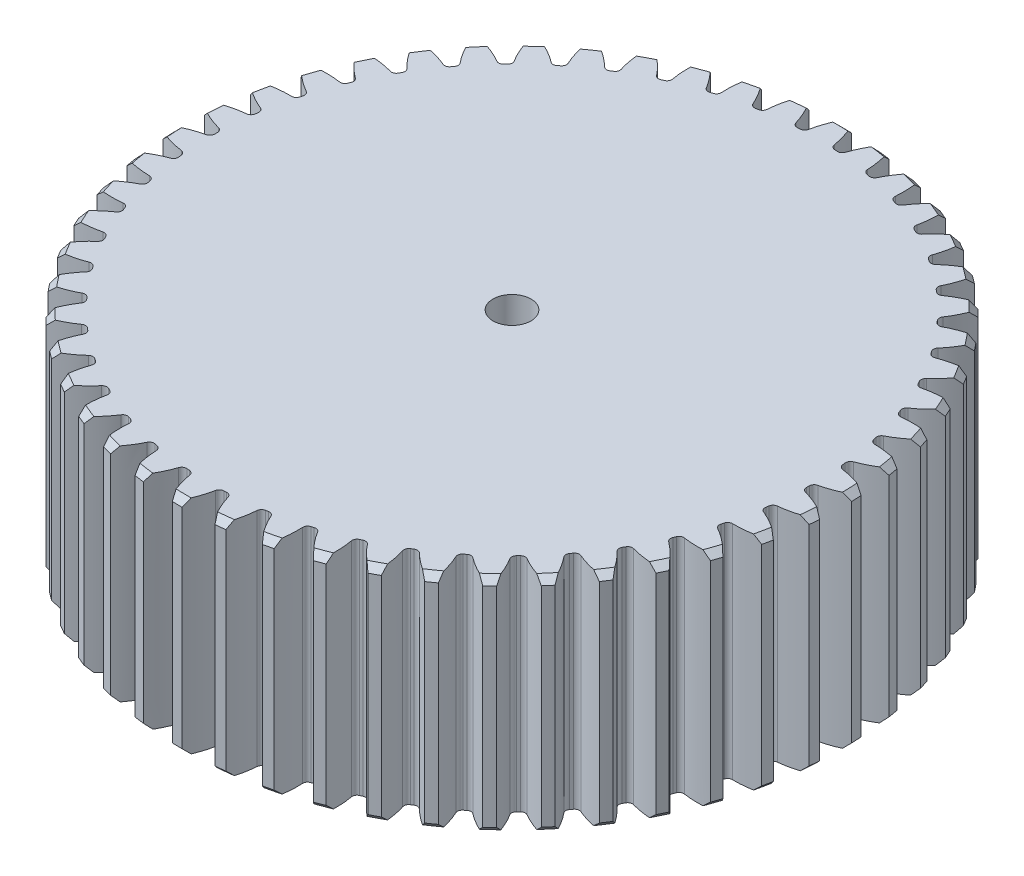
SolidWorks part; units mm, degrees
ref_plane "前视基准面" through (0, 0, 0) normal (0, 0, 1) x (1, 0, 0)
ref_plane "上视基准面" through (0, 0, 0) normal (0, 1, 0) x (1, 0, 0)
ref_plane "右视基准面" through (0, 0, 0) normal (1, 0, 0) x (0, 0, -1)
other "Configuration Table"
sketch "草图2" plane through (0, 0, 0) normal (0, 1, 0) x (1, 0, 0)
  spline S0 degree 4 poles (46.9846, 0) (47.0061, 0.0004) (47.0661, 0.0025) (47.1796, 0.0108) (47.3643, 0.0305) (47.5989, 0.0648) (47.901, 0.1194) (48.2551, 0.197) (48.6421, 0.2962) (49.0604, 0.4189) (49.475, 0.5545) (49.8857, 0.7017) (50.2924, 0.8595) (50.7812, 1.0629) (51.3631, 1.3253) (52.034, 1.6561) (52.7871, 2.0634) (53.5397, 2.5066) (54.2754, 2.9735) (54.9982, 3.466) (55.7019, 3.9762) (56.3971, 4.5131) (56.9817, 4.989) (57.4902, 5.4247) (57.8815, 5.7686) (58.2355, 6.0926) (58.5753, 6.4044) (59.1303, 6.942) (59.4711, 7.2816) (59.9928, 7.8193) (60.1778, 8.0208) (60.3277, 8.1804) knots 0 0 0 0 0 0.005377 0.015084 0.028532 0.04661 0.064855 0.092111 0.119476 0.146842 0.174209 0.201575 0.228941 0.256307 0.307035 0.361767 0.4165 0.471232 0.525964 0.580697 0.635429 0.690161 0.744894 0.77226 0.799626 0.826992 0.854358 0.909091 0.954545 1 1 1 1 1 construction
  spline S1 degree 4 poles (46.9846, 0) (47.0061, 0.0004) (47.0661, 0.0025) (47.1796, 0.0108) (47.3643, 0.0305) (47.5989, 0.0648) (47.901, 0.1194) (48.2551, 0.197) (48.6421, 0.2962) (49.0604, 0.4189) (49.475, 0.5545) (49.8857, 0.7017) (50.2924, 0.8595) (50.7812, 1.0629) (51.3631, 1.3253) (52.034, 1.6561) (52.7871, 2.0634) (53.5397, 2.5066) (54.2754, 2.9735) (54.9982, 3.466) (55.7019, 3.9762) (56.3971, 4.5131) (56.9817, 4.989) (57.4902, 5.4247) (57.8815, 5.7686) (58.2355, 6.0926) (58.5753, 6.4044) (58.9674, 6.7843) (59.1763, 6.9895) (59.3166, 7.1297) knots 0 0 0 0 0 0.005377 0.015084 0.028532 0.04661 0.064855 0.092111 0.119476 0.146842 0.174209 0.201575 0.228941 0.256307 0.307035 0.361767 0.4165 0.471232 0.525964 0.580697 0.635429 0.690161 0.744894 0.77226 0.799626 0.826992 0.854358 0.909091 0.909091 0.909091 0.909091 0.909091
  point P0 (-227.668, 10.3577)
sketch "草图1" plane through (0, 0, 0) normal (0, 1, 0) x (1, 0, 0)
  line L0 (0, 0) -> (58.6395, 2.7181) construction
  circle A0 centre (0, 0) radius 52
  circle A1 centre (0, 0) radius 50 construction
  circle A2 centre (0, 0) radius 47.5
  circle A3 centre (0, 0) radius 46.985 construction
  arc A4 (47.4966, -0.5704) -> (48.0918, 0.1624) centre (48.2565, -0.5796) cw
  arc A5 (47.2401, 4.9618) -> (47.9006, 4.2872) centre (47.996, 5.0412) ccw
  circle A6 centre (0, 0) radius 3
  spline S0 degree 4 poles (47.9006, 4.2872) (47.9869, 4.2763) (48.181, 4.2495) (48.4822, 4.2008) (48.8887, 4.1214) (49.3142, 4.0248) (49.7367, 3.9162) (50.1563, 3.7967) (50.6618, 3.6393) (51.1512, 3.4712) (51.5339, 3.3282) (51.8123, 3.2183) (51.9025, 3.1821) knots 0.070295 0.070295 0.070295 0.070295 0.070295 0.092111 0.119476 0.146842 0.174209 0.201575 0.228941 0.256307 0.307035 0.331424 0.331424 0.331424 0.331424 0.331424
  spline S1 degree 4 poles (46.9846, 0) (46.9847, 0) (46.9848, 0) (46.9849, 0) (46.985, 0) knots 0 0 0 0 0 0.000023 0.000023 0.000023 0.000023 0.000023
  spline S2 degree 4 poles (48.0918, 0.1624) (48.1767, 0.1812) (48.3676, 0.2258) (48.6629, 0.3023) (49.0604, 0.4189) (49.475, 0.5545) (49.8857, 0.7017) (50.2924, 0.8595) (50.7812, 1.0629) (51.2529, 1.2756) (51.6208, 1.4534) (51.8879, 1.5886) (51.9744, 1.633) knots 0.070295 0.070295 0.070295 0.070295 0.070295 0.092111 0.119476 0.146842 0.174209 0.201575 0.228941 0.256307 0.307035 0.331424 0.331424 0.331424 0.331424 0.331424
  point P8 (49.9464, 2.3152)
  point P10 (49.9944, 0.7452)
  dimension "D1" = 104
  dimension "D2" = 100
  dimension "D3" = 95
  dimension "D4" = 93.97
  dimension "D6" = 0.76
  dimension "D5" = 1.57
extrude "凸台-拉伸1" add sketch "草图1" along normal blind 35 contours A2 region at (-46.107, 0, 2.1372)
extrude "凸台-拉伸2" add sketch "草图1<4>" along normal up to surface (35 mm away) contours A4 S2 A0 S0 A5 A2 region at (49.3392, 0, -2.287) up to face at (0, 35, 3)
sketch "草图1<4>" plane through (0, 0, 0) normal (0, 1, 0) x (1, 0, 0) same geometry as "草图1"
chamfer "倒角3" distance 1 angle 45 1 edges at (51.9442, 35, -2.4078)
chamfer "倒角4" distance 1 angle 45 1 edges at (51.9442, 0, -2.4078)
pattern_circular "阵列(圆周)1" count 50 over 360 about axis through (0, 35, 0) along (0, -1, 0) of "凸台-拉伸1", "凸台-拉伸2", "倒角3", "倒角4"
equation "\"m\"= 2'模数"
equation "\"z\" = 50'齿数"
equation "\"a\"= 20'压力角"
equation "\"d\"= \"m\" * \"z\"'分度圆直径"
equation "\"da\"= ( \"z\" + 2 ) * \"m\"'齿顶圆直径"
equation "\"db\"= \"m\" * \"z\" * cos ( \"a\" )'基圆直径"
equation "\"rb\"= \"db\" / 2'基圆半径"
equation "\"s\"= 0.5 * pi * \"m\"'分度圆齿厚"
equation "\"r\"= 0.38 * \"m\"'齿根圆角"
equation "\"df\"= ( \"z\" - 2.5 ) * \"m\"'齿根圆直径"
